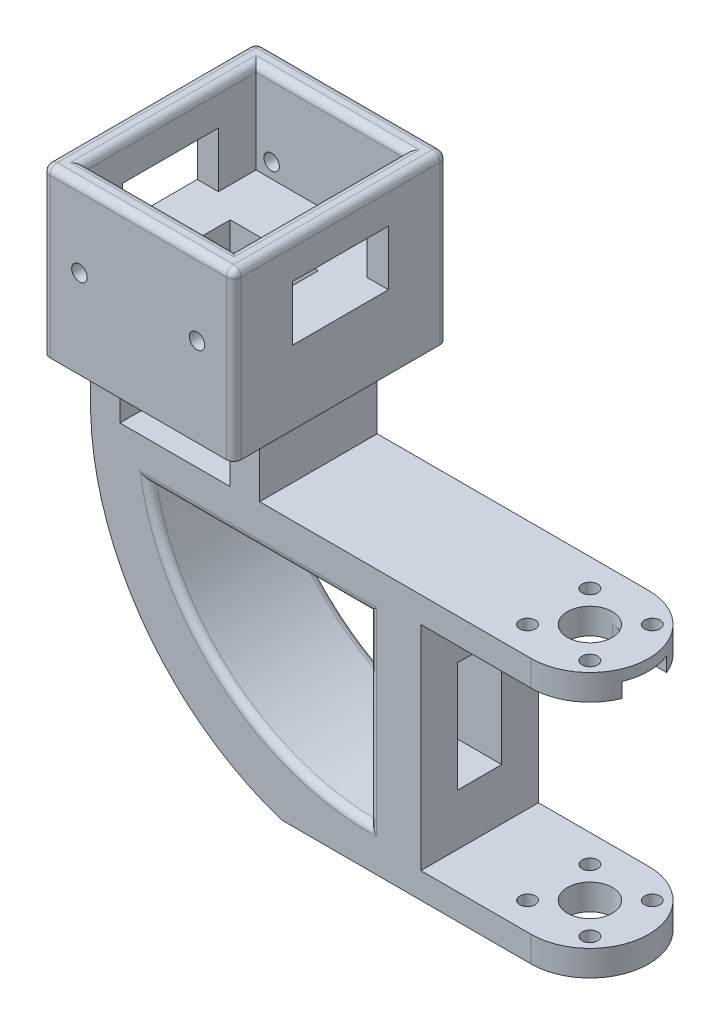
SolidWorks part; units mm, degrees
ref_plane "前视基准面" through (0, 0, 0) normal (0, 0, 1) x (1, 0, 0)
ref_plane "上视基准面" through (0, 0, 0) normal (0, 1, 0) x (1, 0, 0)
ref_plane "右视基准面" through (0, 0, 0) normal (1, 0, 0) x (0, 0, -1)
sketch "草图1" plane through (0, 0, 0) normal (0, 1, 0) x (1, 0, 0)
  line L0 (0, 8) -> (-15, 8)
  line L1 (0, 0) -> (-20.7875, 0) construction
  line L2 (0, -8) -> (-15, -8)
  line L3 (-15, 8) -> (-15, -8)
  line L4 (0, 8) -> (0, -13.8508) construction
  line L5 (0, 0) -> (-10.1753, 10.1753) construction
  line L6 (0, 0) -> (-6.4674, -6.4674) construction
  line L7 (4.2426, 4.2426) -> (-5.3918, -5.3918) construction
  arc A0 (0, -8) -> (0, 8) centre (0, 0) ccw
  circle A1 centre (0, 0) radius 6 construction
  circle A6 centre (0, 0) radius 3.05
  circle A7 centre (-4.2426, 4.2426) radius 1.05
  circle A9 centre (-4.2426, -4.2426) radius 1.05
  circle A10 centre (4.2426, -4.2426) radius 1.05
  circle A11 centre (4.2426, 4.2426) radius 1.05
  dimension "D1" = 16
  dimension "D3" = 12
  dimension "D8" = 6.1
  dimension "D10" = 2.1
  dimension "D13" = 2.1
  dimension "D2" = 15
  dimension "D9" = 45
  dimension "D12" = 45
extrude "凸台-拉伸1" add sketch "草图1" along normal blind 3.5
ref_plane "基准面4" through (0, 18, 0) normal (0, 1, 0) x (1, 0, 0)
mirror "镜向4" about plane through (0, 18, 0) normal (0, 1, 0) of bodies 101
sketch "草图2" plane through (-15, 0, 0) normal (-1, 0, 0) x (0, 0, 1)
  line L0 (-8, 0) -> (8, 0) construction
  line L1 (-8, 36) -> (8, 36)
  line L2 (-8, 36) -> (-8, 0)
  line L3 (-8, 0) -> (8, 0)
  line L4 (8, 36) -> (8, 0)
  line L5 (8, 3.5) -> (8, 0) construction
extrude "凸台-拉伸2" add sketch "草图2" along normal blind 3.5
sketch "草图3" plane through (0, 3.5, 0) normal (0, 1, 0) x (1, 0, 0)
  line L0 (0, -8) -> (10.05, -8)
  line L1 (0, 8) -> (10.05, 8)
  line L2 (10.05, -8) -> (10.05, 8)
  line L3 (0, 8) -> (-15, 8)
  line L4 (-15, 8) -> (-15, -8)
  line L5 (-15, -8) -> (0, -8)
  arc A1 (0, -8) -> (0, 8) centre (0, 0) ccw
  arc A2 (0, -8) -> (0, 8) centre (0, 0) ccw
  dimension "D2" = 25.05
  dimension "D3" = 25.05
  dimension "D1" = 0
sketch "草图4" plane through (-18.5, 0, 0) normal (-1, 0, 0) x (0, 0, 1)
  line L1 (-8, 36) -> (8, 36)
  line L2 (-8, 36) -> (-8, 0)
  line L3 (-8, 0) -> (8, 0)
  line L4 (8, 36) -> (8, 0)
extrude "凸台-拉伸3" add sketch "草图4" along normal blind 41.43
sketch "草图5" plane through (0, 32.5, 0) normal (0, -1, 0) x (1, 0, 0)
  line L0 (0, 3.05) -> (8.871, 3.05)
  line L1 (0, -3.05) -> (10.4418, -3.05)
  line L2 (8.871, 3.05) -> (10.4418, -3.05)
  circle A0 centre (0, 0) radius 3.05 construction
  arc A1 (0, -3.05) -> (0, 3.05) centre (0, 0) ccw
extrude "切除-拉伸1" cut sketch "草图5" against normal blind 2
sketch "草图6" plane through (0, 36, 0) normal (0, 1, 0) x (1, 0, 0)
  line L0 (-59.93, -8) -> (0, -8) construction
  line L1 (-59.93, 8) -> (-36.93, 8)
  line L2 (-59.93, 8) -> (-59.93, -8)
  line L3 (-59.93, -8) -> (-36.93, -8)
  line L4 (-36.93, 8) -> (-36.93, -8)
  dimension "D1" = 23
extrude "凸台-拉伸4" add sketch "草图6" along normal blind 19.21
sketch "草图8" plane through (0, 55.21, 0) normal (0, 1, 0) x (1, 0, 0)
  line L2 (-56.93, 11.515) -> (-36.93, 11.515)
  line L3 (0, 0) -> (-56.93, 0) construction
  line L9 (-56.93, 8) -> (-56.93, -8)
  line L10 (-59.93, 8) -> (-59.93, -8) construction
  line L14 (-56.93, -11.515) -> (-36.93, -11.515)
  line L17 (-59.93, 0) -> (-69.6798, 0) construction
  line L20 (-59.93, 11.515) -> (-59.93, 14.515)
  line L21 (-59.93, 14.515) -> (-36.93, 14.515)
  line L22 (-36.93, 14.515) -> (-36.93, 11.515)
  line L23 (-56.93, 8) -> (-56.93, 11.515)
  line L24 (-59.93, -11.515) -> (-59.93, -14.515)
  line L25 (-59.93, -14.515) -> (-36.93, -14.515)
  line L27 (-36.93, -11.515) -> (-36.93, -14.515)
  line L28 (-56.93, -8) -> (-56.93, -11.515)
  line L29 (-59.93, 11.515) -> (-59.93, 0)
  line L30 (-59.93, 0) -> (-59.93, -11.515)
  dimension "D2" = 3
  dimension "D3" = 3
  dimension "D4" = 3
  dimension "D5" = 23
extrude "凸台-拉伸7" add sketch "草图8" along normal blind 12.5 and the other way blind 10
sketch "草图9" plane through (-56.93, 0, 0) normal (1, 0, 0) x (0, 0, -1)
  line L0 (-8, 55.21) -> (-11.515, 55.21)
  line L1 (-11.515, 45.21) -> (-11.515, 67.71) construction
  line L2 (8, 55.21) -> (11.515, 55.21)
  line L3 (11.515, 45.21) -> (11.515, 67.71) construction
  line L4 (-11.515, 45.21) -> (-8, 45.21)
  line L5 (-11.515, 45.21) -> (-11.515, 67.71) construction
  line L6 (-14.515, 45.21) -> (-11.515, 45.21) construction
  line L7 (11.515, 45.21) -> (8, 45.21)
  line L8 (-11.515, 55.21) -> (-11.515, 45.21)
  line L9 (-8, 55.21) -> (-8, 45.21)
  line L10 (8, 55.21) -> (8, 45.21)
  line L11 (11.515, 55.21) -> (11.515, 45.21)
extrude "凸台-拉伸8" add sketch "草图9" along normal up to surface (20 mm away) up to face at (-36.93, 56.46, 13.015)
sketch "草图10" plane through (-36.93, 0, 0) normal (1, 0, 0) x (0, 0, -1)
  line L0 (-11.515, 67.71) -> (11.515, 67.71)
  line L1 (-8, 45.21) -> (8, 45.21)
  line L12 (-8, 36) -> (8, 36)
  line L13 (8, 36) -> (8, 45.21)
  line L14 (8, 45.21) -> (14.515, 45.21)
  line L15 (14.515, 45.21) -> (14.515, 67.71)
  line L16 (14.515, 67.71) -> (11.515, 67.71)
  line L17 (11.515, 67.71) -> (11.515, 55.21)
  line L18 (11.515, 55.21) -> (-11.515, 55.21)
  line L19 (-11.515, 55.21) -> (-11.515, 67.71)
  line L20 (-11.515, 67.71) -> (-14.515, 67.71)
  line L21 (-14.515, 67.71) -> (-14.515, 45.21)
  line L22 (-14.515, 45.21) -> (-8, 45.21)
  line L23 (-8, 45.21) -> (-8, 36)
  line L26 (8, 45.21) -> (14.515, 45.21)
  line L27 (14.515, 45.21) -> (14.515, 67.71)
  line L28 (14.515, 67.71) -> (11.515, 67.71)
  line L32 (-11.515, 67.71) -> (-14.515, 67.71)
  line L33 (-14.515, 67.71) -> (-14.515, 45.21)
  line L34 (-14.515, 45.21) -> (-8, 45.21)
  dimension "D1" = 0
extrude "凸台-拉伸9" add sketch "草图10" along normal blind 3
sketch "草图11" plane through (0, 0, 11.515) normal (0, 0, -1) x (-1, 0, 0)
  line L0 (46.93, 55.21) -> (46.93, 69.3391) construction
  line L4 (36.93, 67.71) -> (36.93, 55.21)
  line L5 (36.93, 55.21) -> (56.93, 55.21)
  line L6 (56.93, 55.21) -> (56.93, 67.71)
  line L7 (56.93, 67.71) -> (36.93, 67.71)
  line L8 (36.93, 67.71) -> (36.93, 55.21) construction
  line L9 (36.93, 55.21) -> (56.93, 55.21) construction
  line L10 (56.93, 55.21) -> (56.93, 67.71) construction
  line L11 (56.93, 67.71) -> (36.93, 67.71) construction
  circle A0 centre (38.93, 57.21) radius 1.05
  circle A1 centre (54.93, 57.21) radius 1.05
  dimension "D4" = 2.1
  dimension "D2" = 16
  dimension "D3" = 2
  dimension "D1" = 0
extrude "切除-拉伸2" cut sketch "草图11" against normal mid plane 63
sketch "草图12" plane through (0, 0, -8) normal (0, 0, -1) x (-1, 0, 0)
  line L0 (36.93, 36) -> (0, 36) construction
  line L2 (22, 30.5) -> (22, 5.5)
  line L3 (22, 30.5) -> (52, 30.5)
  line L4 (36.93, 45.21) -> (36.93, 36) construction
  line L5 (40.93, 42.21) -> (55.93, 42.21)
  line L6 (15, 32.5) -> (0, 32.5) construction
  line L7 (40.93, 42.21) -> (40.93, 35.777)
  line L8 (15, 3.5) -> (0, 3.5) construction
  line L9 (15, 3.5) -> (15, 32.5) construction
  line L10 (59.9184, 35.0604) -> (67.9823, -21.1711)
  line L11 (67.9823, -21.1711) -> (30.3097, -1.0086)
  line L12 (59.93, 0) -> (59.93, 45.21) construction
  line L14 (40.93, 35.777) -> (55.93, 35.777)
  line L15 (55.93, 42.21) -> (55.93, 35.777)
  line L16 (59.93, 45.21) -> (59.93, 0) construction
  line L17 (36.93, 45.21) -> (59.93, 45.21) construction
  arc A0 (59.9184, 35.0604) -> (30.3097, -1.0086) centre (22, 36) cw
  arc A1 (22, 5.5) -> (52, 30.5) centre (22, 36) ccw
  dimension "D2" = 2
  dimension "D1" = 2
  dimension "D3" = 7
  dimension "D4" = 4
  dimension "D5" = 4
  dimension "D6" = 3
extrude "切除-拉伸3" cut sketch "草图12" against normal through all
sketch "草图13" plane through (0, 42.21, 0) normal (0, -1, 0) x (1, 0, 0)
  line L0 (-59.93, 8) -> (-59.93, -8) construction
  line L1 (-52.93, 4) -> (-40.9451, 4)
  line L2 (-52.93, 4) -> (-52.93, -4)
  line L3 (-52.93, -4) -> (-40.9451, -4)
  line L4 (-40.9451, 4) -> (-40.9451, -4)
  line L5 (-33.9451, 8) -> (-33.9451, -8) construction
  line L6 (-33.9451, 8) -> (-59.9184, 8) construction
  line L7 (-36.93, -8) -> (-59.93, -8) construction
  dimension "D1" = 7
  dimension "D2" = 7
  dimension "D3" = 4
  dimension "D4" = 4
extrude "切除-拉伸4" cut sketch "草图13" against normal up to next
sketch "草图14" plane through (-59.93, 0, 0) normal (-1, 0, 0) x (0, 0, 1)
  line L0 (-14.515, 45.21) -> (-14.515, 67.71) construction
  line L1 (-6.515, 62.71) -> (6.515, 62.71)
  line L2 (-6.515, 62.71) -> (-6.515, 55.21)
  line L3 (-6.515, 55.21) -> (6.515, 55.21)
  line L4 (6.515, 62.71) -> (6.515, 55.21)
  line L5 (14.515, 45.21) -> (14.515, 67.71) construction
  line L6 (-14.515, 67.71) -> (14.515, 67.71) construction
  line L7 (8, 45.21) -> (14.515, 45.21) construction
  dimension "D1" = 8
  dimension "D2" = 8
  dimension "D3" = 5
  dimension "D4" = 10
extrude "切除-拉伸5" cut sketch "草图14" against normal through all
sketch "草图15" plane through (-15, 0, 0) normal (1, 0, 0) x (0, 0, -1)
  line L0 (-8, 3.5) -> (-8, 32.5) construction
  line L1 (-3, 25.5) -> (3, 25.5)
  line L2 (-3, 25.5) -> (-3, 10.5)
  line L3 (-3, 10.5) -> (3, 10.5)
  line L4 (3, 25.5) -> (3, 10.5)
  line L5 (8, 32.5) -> (8, 3.5) construction
  line L6 (-3.05, 32.5) -> (3.05, 32.5) construction
  line L7 (8, 3.5) -> (-8, 3.5) construction
  dimension "D1" = 5
  dimension "D2" = 5
  dimension "D3" = 7
  dimension "D4" = 7
extrude "切除-拉伸6" cut sketch "草图15" against normal up to next
fillet "圆角1" [suppressed] radius 1
ref_plane "基准面5" through (0, 0, 0) normal (0, 0, -1) x (-1, 0, 0)
sketch "草图17" plane through (0, 0, 0) normal (0, 0, -1) x (-1, 0, 0)
  line L4 (36.93, 67.71) -> (36.93, 55.21)
  line L5 (36.93, 55.21) -> (56.93, 55.21)
  line L6 (56.93, 55.21) -> (56.93, 67.71)
  line L7 (56.93, 67.71) -> (36.93, 67.71)
  line L8 (36.93, 67.71) -> (36.93, 55.21)
  line L9 (36.93, 55.21) -> (56.93, 55.21)
  line L10 (56.93, 55.21) -> (56.93, 67.71)
  line L11 (56.93, 67.71) -> (36.93, 67.71)
  dimension "D1" = 0
extrude "切除-拉伸11" cut sketch "草图17" against normal mid plane 23.25
ref_plane "基准面6" through (-46.93, 0, 0) normal (-1, 0, 0) x (0, 0, 1)
sketch "草图18" plane through (-46.93, 0, 0) normal (-1, 0, 0) x (0, 0, 1)
  line L8 (-11.625, 55.21) -> (-6.515, 55.21)
  line L9 (-6.515, 55.21) -> (-6.515, 62.71)
  line L10 (-6.515, 62.71) -> (6.515, 62.71)
  line L11 (6.515, 62.71) -> (6.515, 55.21)
  line L12 (6.515, 55.21) -> (11.625, 55.21)
  line L13 (11.625, 55.21) -> (11.625, 67.71)
  line L14 (11.625, 67.71) -> (-11.625, 67.71)
  line L15 (-11.625, 67.71) -> (-11.625, 55.21)
  line L16 (-11.625, 55.21) -> (-6.515, 55.21)
  line L17 (-6.515, 55.21) -> (-6.515, 62.71)
  line L18 (-6.515, 62.71) -> (6.515, 62.71)
  line L19 (6.515, 62.71) -> (6.515, 55.21)
  line L20 (6.515, 55.21) -> (11.625, 55.21)
  line L21 (11.625, 55.21) -> (11.625, 67.71)
  line L22 (11.625, 67.71) -> (-11.625, 67.71)
  line L23 (-11.625, 67.71) -> (-11.625, 55.21)
  dimension "D1" = 0
extrude "切除-拉伸12" cut sketch "草图18" against normal mid plane 20.25
fillet "圆角2" radius 1 4 edges at (-57.055, 67.71, 0) (-46.93, 67.71, 11.625) (-36.805, 67.71, 0) (-46.93, 67.71, -11.625)
fillet "圆角3" radius 1 4 edges at (-46.93, 67.71, 14.515) (-59.93, 67.71, 0) (-46.93, 67.71, -14.515) (-33.93, 67.71, 0)
fillet "圆角5" radius 1 8 edges at (-34.2229, 67.4171, 14.2221) (-59.6371, 67.4171, 14.2221) (-59.6371, 67.4171, -14.2221) (-34.2229, 67.4171, -14.2221) (-33.93, 55.96, 14.515) (-59.93, 55.96, 14.515) (-59.93, 55.96, -14.515) (-33.93, 55.96, -14.515)
fillet "圆角7" radius 1 6 edges at (-41.5256, 12.5693, -8) (-22, 18, -8) (-37, 30.5, -8) (-22, 18, 8) (-37, 30.5, 8) (-41.5256, 12.5693, 8)
